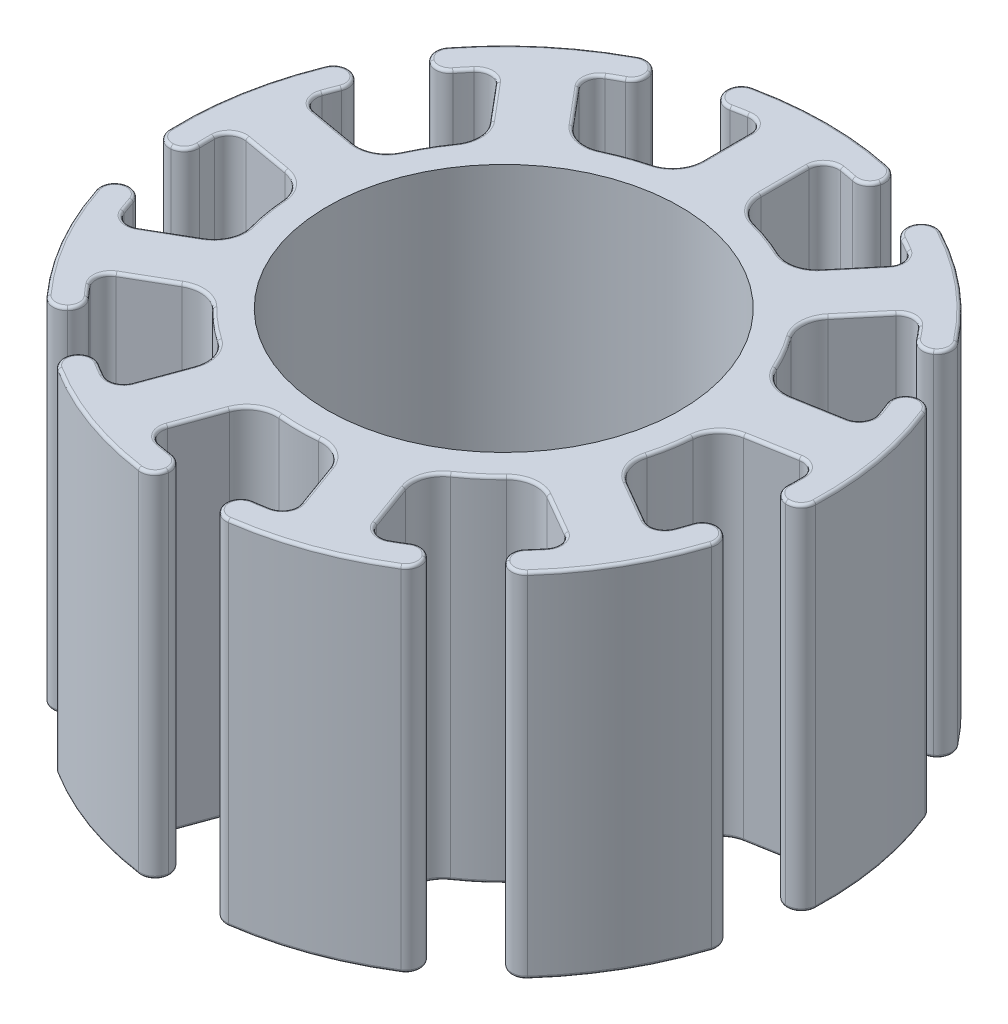
SolidWorks part; units mm, degrees
material "Ductile Iron"
ref_plane "Front Plane" through (0, 0, 0) normal (0, 0, 1) x (1, 0, 0)
ref_plane "Top Plane" through (0, 0, 0) normal (0, 1, 0) x (1, 0, 0)
ref_plane "Right Plane" through (0, 0, 0) normal (1, 0, 0) x (0, 0, -1)
sketch "Sketch1" plane through (0, 0, 0) normal (0, 1, 0) x (1, 0, 0)
  circle A1 centre (0, 0) radius 3.5
  dimension "D1" = 7
extrude "Boss-Extrude1" add sketch "Sketch1" along normal mid plane 6
ref_axis "Axis1" through (0, 3, 0) along (0, -1, 0)
sketch "Sketch2" plane through (0, 3, 0) normal (0, 1, 0) x (1, 0, 0)
  line L0 (0, 0) -> (0, 5.5) construction
  line L1 (-1.4, 5.3188) -> (-1.2727, 4.8353)
  line L2 (1.4, 5.3188) -> (1.2727, 4.8353)
  line L3 (-0.5, 4.9749) -> (-0.5, 3.4641)
  line L4 (0.5, 4.9749) -> (0.5, 3.4641)
  circle A0 centre (0, 0) radius 3.5 construction
  arc A1 (0.5, 3.4641) -> (-0.5, 3.4641) centre (0, 0) ccw
  arc A2 (1.4, 5.3188) -> (-1.4, 5.3188) centre (0, 0) ccw
  arc A3 (1.2727, 4.8353) -> (0.5, 4.9749) centre (0, 0) ccw
  arc A4 (-0.5, 4.9749) -> (-1.2727, 4.8353) centre (0, 0) ccw
  dimension "D1" = 5.5
  dimension "D2" = 0.5
  dimension "D3" = 1
  dimension "D4" = 2.8
extrude "Boss-Extrude2" add sketch "Sketch2" against normal up to surface (6 mm away) up to face at (0, -3, 3.5)
fillet "Fillet1" radius 0.25 6 edges at (-0.5, 0, -4.9749) (0.5, 0, -4.9749) (1.4, 0, -5.3188) (1.2727, 0, -4.8353) (-1.4, 0, -5.3188) (-1.2727, 0, -4.8353)
pattern_circular "CirPattern1" count 9 over 360 about axis through (0, 3, 0) along (0, -1, 0) of "Boss-Extrude2", "Fillet1"
fillet "Fillet2" radius 0.5 18 edges at (-1.8437, 0, -2.975) (-2.6097, 0, -2.3323) (-3.3247, 0, -1.0939) (-3.4983, 0, -0.1091) (-3.25, 0, 1.299) (-2.75, 0, 2.1651) (-1.6546, 0, 3.0842) (-0.7149, 0, 3.4262) (0.7149, 0, 3.4262) (1.6546, 0, 3.0842) (2.75, 0, 2.1651) (3.4983, 0, -0.1091) (0.5, 0, -3.4641) (2.6097, 0, -2.3323) (3.25, 0, 1.299) (3.3247, 0, -1.0939) (1.8437, 0, -2.975) (-0.5, 0, -3.4641)
sketch "Sketch3" plane through (0, 3, 0) normal (0, 1, 0) x (1, 0, 0)
  circle A0 centre (0, 0) radius 3
  dimension "D1" = 6
extrude "Cut-Extrude1" cut sketch "Sketch3" against normal through all
fillet "Fillet3" radius 0.05 46 edges at (-2.6869, -3, -4.1166) (-2.4582, -3, -4.354) (2.4582, -3, -4.354) (2.6869, -3, -4.1166) (2.3692, -3, -3.6014) (1.8295, -3, -3.121) (1.1971, -3, -3.2889) (0.6047, -3, -3.5668) (0.5, -3, -4.2817) (0.5878, -3, -4.8806) (0.9156, -3, -4.9155) (1.2241, -3, -4.9221) (1.306, -3, -5.266) (0, -3, -5.5) (-1.306, -3, -5.266) (-1.2241, -3, -4.9221) (-0.9156, -3, -4.9155) (-0.5878, -3, -4.8806) (-0.5, -3, -4.2817) (-0.6047, -3, -3.5668) (-1.1971, -3, -3.2889) (-1.8295, -3, -3.121) (-0.6047, 3, -3.5668) (-0.5, 3, -4.2817) (-0.5878, 3, -4.8806) (-0.9156, 3, -4.9155) (-1.2241, 3, -4.9221) (-1.306, 3, -5.266) (0, 3, -5.5) (1.306, 3, -5.266) (1.2241, 3, -4.9221) (0.9156, 3, -4.9155) (0.5878, 3, -4.8806) (0.5, 3, -4.2817) (0.6047, 3, -3.5668) (1.1971, 3, -3.2889) (1.8295, 3, -3.121) (2.3692, 3, -3.6014) (2.6869, 3, -4.1166) (2.4582, 3, -4.354) (-2.4582, 3, -4.354) (-2.6869, 3, -4.1166) (-2.3692, 3, -3.6014) (-1.8295, 3, -3.121) (-1.1971, 3, -3.2889) (-2.3692, -3, -3.6014)
